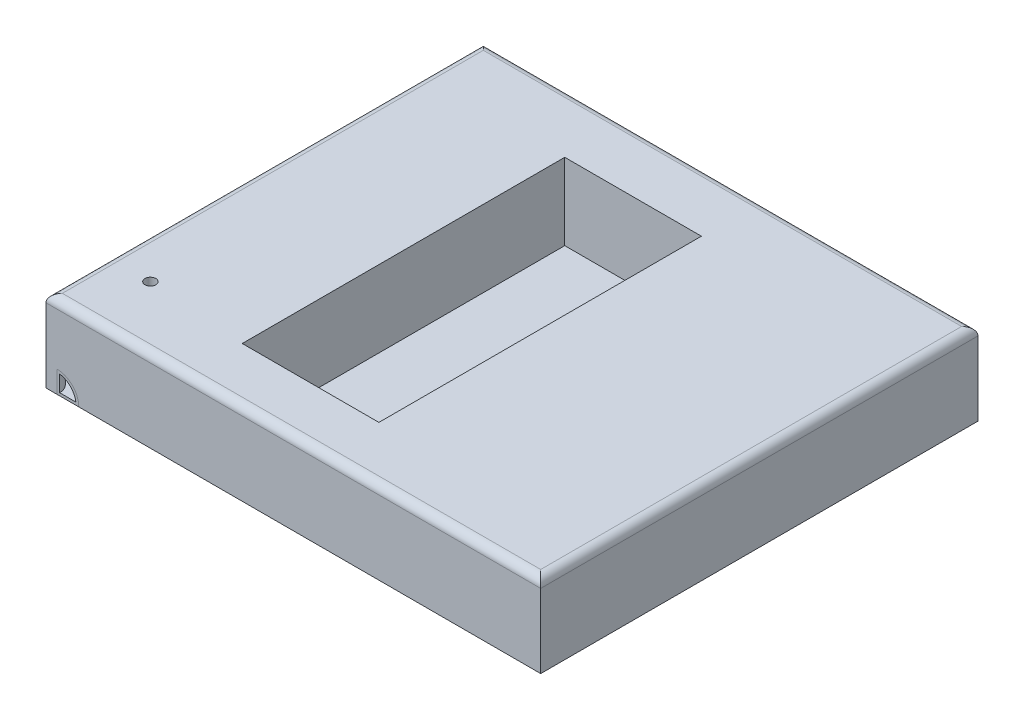
SolidWorks part; units mm, degrees
ref_plane "Front Plane" through (0, 0, 0) normal (0, 0, 1) x (1, 0, 0)
ref_plane "Top Plane" through (0, 0, 0) normal (0, 1, 0) x (1, 0, 0)
ref_plane "Right Plane" through (0, 0, 0) normal (1, 0, 0) x (0, 0, -1)
sketch "Sketch1" plane through (0, 0, 0) normal (0, 1, 0) x (1, 0, 0)
  line L1 (-45.25, -40) -> (45.25, -40)
  line L2 (-45.25, -40) -> (-45.25, 40)
  line L3 (-45.25, 40) -> (45.25, 40)
  line L4 (45.25, -40) -> (45.25, 40)
  line L5 (-45.25, -40) -> (45.25, 40) construction
  line L6 (-45.25, 40) -> (45.25, -40) construction
  point P0 (0, 0)
  dimension "D1" = 80
  dimension "D2" = 90.5
extrude "Boss-Extrude1" add sketch "Sketch1" along normal blind 15
shell "Shell3" thickness 1.5 removed face at (0, 0, 0)
sketch "Sketch4" plane through (-45.25, 0, 0) normal (-1, 0, 0) x (0, 0, 1)
  line L0 (-34.3, 1.6) -> (-28.56, 1.6) construction
  line L1 (-34.3, 3.2) -> (-28.56, 3.2)
  line L2 (-34.3, 0) -> (-28.56, 0)
  arc A0 (-34.3, 3.2) -> (-34.3, 0) centre (-34.3, 1.6) ccw
  arc A1 (-28.56, 0) -> (-28.56, 3.2) centre (-28.56, 1.6) ccw
  point P2 (-31.43, 1.6)
extrude "Cut-Extrude2" cut sketch "Sketch4" against normal blind 1.5
sketch "Sketch6" plane through (-45.25, 0, 0) normal (-1, 0, 0) x (0, 0, 1)
  line L0 (-28.56, 0) -> (40, 0) construction
  line L1 (-24.15, 7.1) -> (-11, 7.1)
  line L2 (-24.15, 7.1) -> (-24.15, 0)
  line L3 (-24.15, 0) -> (-11, 0)
  line L4 (-11, 7.1) -> (-11, 0)
  line L5 (-24.15, 7.1) -> (-11, 0) construction
  line L6 (-24.15, 0) -> (-11, 7.1) construction
  line L7 (-40, 15) -> (-40, 0) construction
  dimension "D1" = 7.1
  dimension "D2" = 13.15
  dimension "D3" = 0
  dimension "D4" = 15.85
extrude "Cut-Extrude3" cut sketch "Sketch6" against normal blind 1.5
sketch "Sketch9" plane through (-45.25, 0, 0) normal (-1, 0, 0) x (0, 0, 1)
  line L0 (-28.56, 0) -> (-24.15, 0) construction
  line L1 (-25.65, 0) -> (-9.5, 0)
  line L2 (-25.65, 0) -> (-25.65, 1.55)
  line L3 (-25.65, 1.55) -> (-9.5, 1.55)
  line L4 (-9.5, 0) -> (-9.5, 1.55)
  line L5 (-11, 0) -> (-11, 7.1) construction
  dimension "D1" = 16.15
  dimension "D2" = 1.55
  dimension "D3" = 1.5
extrude "Boss-Extrude2" add sketch "Sketch9" along normal blind 1.5
sketch "Sketch11" plane through (0, 15, 0) normal (0, 1, 0) x (1, 0, 0)
  line L1 (-45.25, 40) -> (-45.25, -40) construction
  circle A0 centre (-37.55, -28.6) radius 1
  point P5 (-120.6148, 3.2069)
  point P6 (-122.9279, 20.4506)
  dimension "D1" = 7.7
fillet "Fillet7" radius 1.5 4 edges at (45.25, 15, 0) (0, 15, 40) (0, 15, -40) (-45.25, 15, 0)
sketch "Sketch20" plane through (0, 15, 0) normal (0, 1, 0) x (1, 0, 0)
  line L0 (-45.25, 40) -> (45.25, 40) construction
  line L1 (5.65, 29) -> (-19.35, 29)
  line L2 (5.65, 29) -> (5.65, -30)
  line L3 (5.65, -30) -> (-19.35, -30)
  line L4 (-19.35, 29) -> (-19.35, -30)
  line L6 (-43.75, 38.5) -> (-43.75, -38.5) construction
  dimension "D1" = 11
  dimension "D2" = 59
  dimension "D3" = 24.4
  dimension "D4" = 25
extrude "Boss-Extrude8" add sketch "Sketch20" against normal blind 14
extrude "Cut-Extrude9" cut sketch "Sketch20<2>" against normal blind 1.5
sketch "Sketch20<2>" plane through (0, 15, 0) normal (0, 1, 0) x (1, 0, 0) same geometry as "Sketch20"
shell "Shell6" thickness 1 removed face at (-6.85, 13.5, 0.5) outward yes
sketch "Sketch21" plane through (0, 13.5, 0) normal (0, -1, 0) x (-1, 0, 0)
  line L0 (43.75, -38.5) -> (-43.75, -38.5) construction
  line L1 (-6.65, -31) -> (-5.65, -31)
  line L2 (-6.65, -31) -> (-6.65, -38.5)
  line L3 (-6.65, -38.5) -> (-5.65, -38.5)
  line L4 (-5.65, -31) -> (-5.65, -38.5)
  line L5 (-43.75, 38.5) -> (43.75, 38.5) construction
  line L6 (-6.65, 30) -> (-5.65, 30)
  line L7 (-6.65, 30) -> (-6.65, 38.5)
  line L8 (-6.65, 38.5) -> (-5.65, 38.5)
  line L9 (-5.65, 30) -> (-5.65, 38.5)
  dimension "D1" = 1
  dimension "D2" = 1
extrude "Boss-Extrude9" add sketch "Sketch21" along normal blind 13.5
extrude "Boss-Extrude10" add sketch "Sketch11" against normal blind 10
extrude "Cut-Extrude10" cut sketch "Sketch11<3>" against normal blind 1.5
sketch "Sketch11<3>" plane through (0, 15, 0) normal (0, 1, 0) x (1, 0, 0) same geometry as "Sketch11"
shell "Shell9" thickness 1 removed face at (-37.55, 5, 29.6) removed face at (-37.55, 13.5, 29.6) outward yes
sketch "Sketch33" plane through (0, 0, 40) normal (0, 0, 1) x (1, 0, 0)
  line L3 (-45.25, 0) -> (45.25, 0) construction
  line L6 (-43.25, 4) -> (-43.25, 0)
  line L7 (-43.25, 0) -> (-39.25, 0)
  arc A2 (-43.25, 4) -> (-39.25, 0) centre (-43.25, 0) cw
  dimension "D1" = 2
revolve "Cut-Revolve4" cut sketch "Sketch33" angle 90 about axis through (-45.25, 15, 40) along (0, -1, 0) reverse direction yes
revolve "Revolve3" add sketch "Sketch33<2>" angle 90 about axis through (-45.25, 15, 40) along (0, -1, 0) reverse direction yes
sketch "Sketch33<2>" plane through (0, 0, 40) normal (0, 0, 1) x (1, 0, 0) same geometry as "Sketch33"
shell "Shell14" thickness 0.5 removed face at (-45.25, 1.6095, 36.3905) removed face at (-41.6405, 1.6095, 40)
